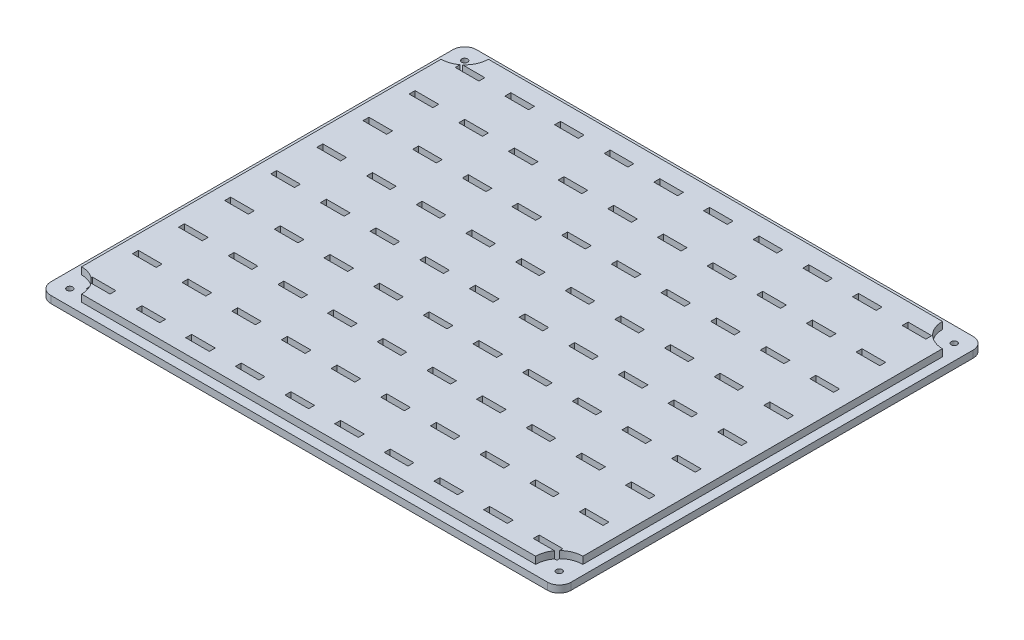
SolidWorks part; units mm, degrees
ref_plane "Front Plane" through (0, 0, 0) normal (0, 0, 1) x (1, 0, 0)
ref_plane "Top Plane" through (0, 0, 0) normal (0, 1, 0) x (1, 0, 0)
ref_plane "Right Plane" through (0, 0, 0) normal (1, 0, 0) x (0, 0, -1)
sketch "Sketch1" plane through (0, 0, 0) normal (0, 1, 0) x (1, 0, 0)
  line L1 (0, 0) -> (220, 0)
  line L2 (0, 0) -> (0, 180)
  line L3 (0, 180) -> (220, 180)
  line L4 (220, 0) -> (220, 180)
  dimension "D1" = 220
  dimension "D2" = 180
extrude "Boss-Extrude1" add sketch "Sketch1" along normal blind 3
fillet "Fillet1" radius 5 4 edges at (0, 1.5, -180) (0, 1.5, 0) (220, 1.5, -180) (220, 1.5, 0)
sketch "Sketch7" plane through (0, 3, 0) normal (0, 1, 0) x (1, 0, 0)
  line L0 (110, 187.4123) -> (110, -2.139) construction
  line L1 (-6.8646, 90) -> (231.1986, 90) construction
  line L2 (206, 176) -> (14, 176)
  line L3 (216, 166) -> (216, 14)
  line L4 (215, 180) -> (5, 180) construction
  line L5 (220, 5) -> (220, 175) construction
  line L6 (206, 4) -> (14, 4)
  line L7 (4, 166) -> (4, 14)
  line L8 (0, 175) -> (0, 5) construction
  line L9 (5, 0) -> (215, 0) construction
  arc A0 (206, 176) -> (216, 166) centre (216, 176) ccw
  arc A1 (206, 4) -> (216, 14) centre (216, 4) cw
  arc A2 (14, 4) -> (4, 14) centre (4, 4) ccw
  arc A3 (14, 176) -> (4, 166) centre (4, 176) cw
  point P14 (216, 90)
  point P18 (110, 4)
  point P23 (110, 176)
  dimension "D5" = 4
  dimension "D1" = 4
  dimension "D2" = 4
  dimension "D3" = 14
  dimension "D4" = 14
  dimension "D6" = 4
extrude "Boss-Extrude2" add sketch "Sketch7" along normal blind 3
sketch "Sketch8" plane through (0, 3, 0) normal (0, 1, 0) x (1, 0, 0)
  line L0 (110, 176) -> (110, 4) construction
  line L1 (206, 176) -> (14, 176) construction
  line L2 (14, 4) -> (206, 4) construction
  line L3 (4, 90) -> (216, 90) construction
  line L4 (4, 166) -> (4, 14) construction
  line L5 (216, 14) -> (216, 166) construction
  line L6 (215, 180) -> (5, 180) construction
  line L7 (0, 175) -> (0, 5) construction
  circle A0 centre (6.5, 173.5) radius 1.25
  circle A1 centre (213.5, 173.5) radius 1.25
  circle A2 centre (213.5, 6.5) radius 1.25
  circle A3 centre (6.5, 6.5) radius 1.25
  dimension "D2" = 6.5
  dimension "D3" = 6.5
extrude "Cut-Extrude3" cut sketch "Sketch8" against normal through all
sketch "Sketch9" plane through (0, 0, 0) normal (0, -1, 0) x (1, 0, 0)
  line L6 (31, -10) -> (31, -12.5)
  line L9 (31, -10) -> (41, -10)
  line L10 (10, -10) -> (20, -10)
  line L11 (10, -10) -> (10, -12.5)
  line L12 (10, -12.5) -> (20, -12.5)
  line L13 (20, -10) -> (20, -12.5)
  line L14 (41, -10) -> (41, -12.5)
  line L15 (31, -12.5) -> (41, -12.5)
  line L16 (52, -10) -> (52, -12.5)
  line L17 (52, -10) -> (62, -10)
  line L18 (62, -10) -> (62, -12.5)
  line L19 (52, -12.5) -> (62, -12.5)
  line L20 (73, -10) -> (73, -12.5)
  line L21 (73, -10) -> (83, -10)
  line L22 (83, -10) -> (83, -12.5)
  line L23 (73, -12.5) -> (83, -12.5)
  line L24 (94, -10) -> (94, -12.5)
  line L25 (94, -10) -> (104, -10)
  line L26 (104, -10) -> (104, -12.5)
  line L27 (94, -12.5) -> (104, -12.5)
  line L28 (115, -10) -> (115, -12.5)
  line L29 (115, -10) -> (125, -10)
  line L30 (125, -10) -> (125, -12.5)
  line L31 (115, -12.5) -> (125, -12.5)
  line L32 (136, -10) -> (136, -12.5)
  line L33 (136, -10) -> (146, -10)
  line L34 (146, -10) -> (146, -12.5)
  line L35 (136, -12.5) -> (146, -12.5)
  line L36 (157, -10) -> (157, -12.5)
  line L37 (157, -10) -> (167, -10)
  line L38 (167, -10) -> (167, -12.5)
  line L39 (157, -12.5) -> (167, -12.5)
  line L40 (178, -10) -> (178, -12.5)
  line L41 (178, -10) -> (188, -10)
  line L42 (188, -10) -> (188, -12.5)
  line L43 (178, -12.5) -> (188, -12.5)
  line L44 (199, -10) -> (199, -12.5)
  line L45 (199, -10) -> (209, -10)
  line L46 (209, -10) -> (209, -12.5)
  line L47 (199, -12.5) -> (209, -12.5)
  line L48 (31, -29.5) -> (31, -32)
  line L49 (31, -29.5) -> (41, -29.5)
  line L50 (41, -29.5) -> (41, -32)
  line L51 (31, -32) -> (41, -32)
  line L52 (52, -29.5) -> (52, -32)
  line L53 (52, -29.5) -> (62, -29.5)
  line L54 (62, -29.5) -> (62, -32)
  line L55 (52, -32) -> (62, -32)
  line L56 (73, -29.5) -> (73, -32)
  line L57 (73, -29.5) -> (83, -29.5)
  line L58 (83, -29.5) -> (83, -32)
  line L59 (73, -32) -> (83, -32)
  line L60 (94, -29.5) -> (94, -32)
  line L61 (94, -29.5) -> (104, -29.5)
  line L62 (104, -29.5) -> (104, -32)
  line L63 (94, -32) -> (104, -32)
  line L64 (115, -29.5) -> (115, -32)
  line L65 (115, -29.5) -> (125, -29.5)
  line L66 (125, -29.5) -> (125, -32)
  line L67 (115, -32) -> (125, -32)
  line L68 (136, -29.5) -> (136, -32)
  line L69 (136, -29.5) -> (146, -29.5)
  line L70 (146, -29.5) -> (146, -32)
  line L71 (136, -32) -> (146, -32)
  line L72 (157, -29.5) -> (157, -32)
  line L73 (157, -29.5) -> (167, -29.5)
  line L74 (167, -29.5) -> (167, -32)
  line L75 (157, -32) -> (167, -32)
  line L76 (178, -29.5) -> (178, -32)
  line L77 (178, -29.5) -> (188, -29.5)
  line L78 (188, -29.5) -> (188, -32)
  line L79 (178, -32) -> (188, -32)
  line L80 (199, -29.5) -> (199, -32)
  line L81 (199, -29.5) -> (209, -29.5)
  line L82 (209, -29.5) -> (209, -32)
  line L83 (199, -32) -> (209, -32)
  line L84 (31, -49) -> (31, -51.5)
  line L85 (31, -49) -> (41, -49)
  line L86 (41, -49) -> (41, -51.5)
  line L87 (31, -51.5) -> (41, -51.5)
  line L88 (52, -49) -> (52, -51.5)
  line L89 (52, -49) -> (62, -49)
  line L90 (62, -49) -> (62, -51.5)
  line L91 (52, -51.5) -> (62, -51.5)
  line L92 (73, -49) -> (73, -51.5)
  line L93 (73, -49) -> (83, -49)
  line L94 (83, -49) -> (83, -51.5)
  line L95 (73, -51.5) -> (83, -51.5)
  line L96 (94, -49) -> (94, -51.5)
  line L97 (94, -49) -> (104, -49)
  line L98 (104, -49) -> (104, -51.5)
  line L99 (94, -51.5) -> (104, -51.5)
  line L100 (115, -49) -> (115, -51.5)
  line L101 (115, -49) -> (125, -49)
  line L102 (125, -49) -> (125, -51.5)
  line L103 (115, -51.5) -> (125, -51.5)
  line L104 (136, -49) -> (136, -51.5)
  line L105 (136, -49) -> (146, -49)
  line L106 (146, -49) -> (146, -51.5)
  line L107 (136, -51.5) -> (146, -51.5)
  line L108 (157, -49) -> (157, -51.5)
  line L109 (157, -49) -> (167, -49)
  line L110 (167, -49) -> (167, -51.5)
  line L111 (157, -51.5) -> (167, -51.5)
  line L112 (178, -49) -> (178, -51.5)
  line L113 (178, -49) -> (188, -49)
  line L114 (188, -49) -> (188, -51.5)
  line L115 (178, -51.5) -> (188, -51.5)
  line L116 (199, -49) -> (199, -51.5)
  line L117 (199, -49) -> (209, -49)
  line L118 (209, -49) -> (209, -51.5)
  line L119 (199, -51.5) -> (209, -51.5)
  line L120 (31, -68.5) -> (31, -71)
  line L121 (31, -68.5) -> (41, -68.5)
  line L122 (41, -68.5) -> (41, -71)
  line L123 (31, -71) -> (41, -71)
  line L124 (52, -68.5) -> (52, -71)
  line L125 (52, -68.5) -> (62, -68.5)
  line L126 (62, -68.5) -> (62, -71)
  line L127 (52, -71) -> (62, -71)
  line L128 (73, -68.5) -> (73, -71)
  line L129 (73, -68.5) -> (83, -68.5)
  line L130 (83, -68.5) -> (83, -71)
  line L131 (73, -71) -> (83, -71)
  line L132 (94, -68.5) -> (94, -71)
  line L133 (94, -68.5) -> (104, -68.5)
  line L134 (104, -68.5) -> (104, -71)
  line L135 (94, -71) -> (104, -71)
  line L136 (115, -68.5) -> (115, -71)
  line L137 (115, -68.5) -> (125, -68.5)
  line L138 (125, -68.5) -> (125, -71)
  line L139 (115, -71) -> (125, -71)
  line L140 (136, -68.5) -> (136, -71)
  line L141 (136, -68.5) -> (146, -68.5)
  line L142 (146, -68.5) -> (146, -71)
  line L143 (136, -71) -> (146, -71)
  line L144 (157, -68.5) -> (157, -71)
  line L145 (157, -68.5) -> (167, -68.5)
  line L146 (167, -68.5) -> (167, -71)
  line L147 (157, -71) -> (167, -71)
  line L148 (178, -68.5) -> (178, -71)
  line L149 (178, -68.5) -> (188, -68.5)
  line L150 (188, -68.5) -> (188, -71)
  line L151 (178, -71) -> (188, -71)
  line L152 (199, -68.5) -> (199, -71)
  line L153 (199, -68.5) -> (209, -68.5)
  line L154 (209, -68.5) -> (209, -71)
  line L155 (199, -71) -> (209, -71)
  line L156 (31, -88) -> (31, -90.5)
  line L157 (31, -88) -> (41, -88)
  line L158 (41, -88) -> (41, -90.5)
  line L159 (31, -90.5) -> (41, -90.5)
  line L160 (52, -88) -> (52, -90.5)
  line L161 (52, -88) -> (62, -88)
  line L162 (62, -88) -> (62, -90.5)
  line L163 (52, -90.5) -> (62, -90.5)
  line L164 (73, -88) -> (73, -90.5)
  line L165 (73, -88) -> (83, -88)
  line L166 (83, -88) -> (83, -90.5)
  line L167 (73, -90.5) -> (83, -90.5)
  line L168 (94, -88) -> (94, -90.5)
  line L169 (94, -88) -> (104, -88)
  line L170 (104, -88) -> (104, -90.5)
  line L171 (94, -90.5) -> (104, -90.5)
  line L172 (115, -88) -> (115, -90.5)
  line L173 (115, -88) -> (125, -88)
  line L174 (125, -88) -> (125, -90.5)
  line L175 (115, -90.5) -> (125, -90.5)
  line L176 (136, -88) -> (136, -90.5)
  line L177 (136, -88) -> (146, -88)
  line L178 (146, -88) -> (146, -90.5)
  line L179 (136, -90.5) -> (146, -90.5)
  line L180 (157, -88) -> (157, -90.5)
  line L181 (157, -88) -> (167, -88)
  line L182 (167, -88) -> (167, -90.5)
  line L183 (157, -90.5) -> (167, -90.5)
  line L184 (178, -88) -> (178, -90.5)
  line L185 (178, -88) -> (188, -88)
  line L186 (188, -88) -> (188, -90.5)
  line L187 (178, -90.5) -> (188, -90.5)
  line L188 (199, -88) -> (199, -90.5)
  line L189 (199, -88) -> (209, -88)
  line L190 (209, -88) -> (209, -90.5)
  line L191 (199, -90.5) -> (209, -90.5)
  line L192 (31, -107.5) -> (31, -110)
  line L193 (31, -107.5) -> (41, -107.5)
  line L194 (41, -107.5) -> (41, -110)
  line L195 (31, -110) -> (41, -110)
  line L196 (52, -107.5) -> (52, -110)
  line L197 (52, -107.5) -> (62, -107.5)
  line L198 (62, -107.5) -> (62, -110)
  line L199 (52, -110) -> (62, -110)
  line L200 (73, -107.5) -> (73, -110)
  line L201 (73, -107.5) -> (83, -107.5)
  line L202 (83, -107.5) -> (83, -110)
  line L203 (73, -110) -> (83, -110)
  line L204 (94, -107.5) -> (94, -110)
  line L205 (94, -107.5) -> (104, -107.5)
  line L206 (104, -107.5) -> (104, -110)
  line L207 (94, -110) -> (104, -110)
  line L208 (115, -107.5) -> (115, -110)
  line L209 (115, -107.5) -> (125, -107.5)
  line L210 (125, -107.5) -> (125, -110)
  line L211 (115, -110) -> (125, -110)
  line L212 (136, -107.5) -> (136, -110)
  line L213 (136, -107.5) -> (146, -107.5)
  line L214 (146, -107.5) -> (146, -110)
  line L215 (136, -110) -> (146, -110)
  line L216 (157, -107.5) -> (157, -110)
  line L217 (157, -107.5) -> (167, -107.5)
  line L218 (167, -107.5) -> (167, -110)
  line L219 (157, -110) -> (167, -110)
  line L220 (178, -107.5) -> (178, -110)
  line L221 (178, -107.5) -> (188, -107.5)
  line L222 (188, -107.5) -> (188, -110)
  line L223 (178, -110) -> (188, -110)
  line L224 (199, -107.5) -> (199, -110)
  line L225 (199, -107.5) -> (209, -107.5)
  line L226 (209, -107.5) -> (209, -110)
  line L227 (199, -110) -> (209, -110)
  line L228 (31, -127) -> (31, -129.5)
  line L229 (31, -127) -> (41, -127)
  line L230 (41, -127) -> (41, -129.5)
  line L231 (31, -129.5) -> (41, -129.5)
  line L232 (52, -127) -> (52, -129.5)
  line L233 (52, -127) -> (62, -127)
  line L234 (62, -127) -> (62, -129.5)
  line L235 (52, -129.5) -> (62, -129.5)
  line L236 (73, -127) -> (73, -129.5)
  line L237 (73, -127) -> (83, -127)
  line L238 (83, -127) -> (83, -129.5)
  line L239 (73, -129.5) -> (83, -129.5)
  line L240 (94, -127) -> (94, -129.5)
  line L241 (94, -127) -> (104, -127)
  line L242 (104, -127) -> (104, -129.5)
  line L243 (94, -129.5) -> (104, -129.5)
  line L244 (115, -127) -> (115, -129.5)
  line L245 (115, -127) -> (125, -127)
  line L246 (125, -127) -> (125, -129.5)
  line L247 (115, -129.5) -> (125, -129.5)
  line L248 (136, -127) -> (136, -129.5)
  line L249 (136, -127) -> (146, -127)
  line L250 (146, -127) -> (146, -129.5)
  line L251 (136, -129.5) -> (146, -129.5)
  line L252 (157, -127) -> (157, -129.5)
  line L253 (157, -127) -> (167, -127)
  line L254 (167, -127) -> (167, -129.5)
  line L255 (157, -129.5) -> (167, -129.5)
  line L256 (178, -127) -> (178, -129.5)
  line L257 (178, -127) -> (188, -127)
  line L258 (188, -127) -> (188, -129.5)
  line L259 (178, -129.5) -> (188, -129.5)
  line L260 (199, -127) -> (199, -129.5)
  line L261 (199, -127) -> (209, -127)
  line L262 (209, -127) -> (209, -129.5)
  line L263 (199, -129.5) -> (209, -129.5)
  line L264 (31, -146.5) -> (31, -149)
  line L265 (31, -146.5) -> (41, -146.5)
  line L266 (41, -146.5) -> (41, -149)
  line L267 (31, -149) -> (41, -149)
  line L268 (52, -146.5) -> (52, -149)
  line L269 (52, -146.5) -> (62, -146.5)
  line L270 (62, -146.5) -> (62, -149)
  line L271 (52, -149) -> (62, -149)
  line L272 (73, -146.5) -> (73, -149)
  line L273 (73, -146.5) -> (83, -146.5)
  line L274 (83, -146.5) -> (83, -149)
  line L275 (73, -149) -> (83, -149)
  line L276 (94, -146.5) -> (94, -149)
  line L277 (94, -146.5) -> (104, -146.5)
  line L278 (104, -146.5) -> (104, -149)
  line L279 (94, -149) -> (104, -149)
  line L280 (115, -146.5) -> (115, -149)
  line L281 (115, -146.5) -> (125, -146.5)
  line L282 (125, -146.5) -> (125, -149)
  line L283 (115, -149) -> (125, -149)
  line L284 (136, -146.5) -> (136, -149)
  line L285 (136, -146.5) -> (146, -146.5)
  line L286 (146, -146.5) -> (146, -149)
  line L287 (136, -149) -> (146, -149)
  line L288 (157, -146.5) -> (157, -149)
  line L289 (157, -146.5) -> (167, -146.5)
  line L290 (167, -146.5) -> (167, -149)
  line L291 (157, -149) -> (167, -149)
  line L292 (178, -146.5) -> (178, -149)
  line L293 (178, -146.5) -> (188, -146.5)
  line L294 (188, -146.5) -> (188, -149)
  line L295 (178, -149) -> (188, -149)
  line L296 (199, -146.5) -> (199, -149)
  line L297 (199, -146.5) -> (209, -146.5)
  line L298 (209, -146.5) -> (209, -149)
  line L299 (199, -149) -> (209, -149)
  line L300 (31, -166) -> (31, -168.5)
  line L301 (31, -166) -> (41, -166)
  line L302 (41, -166) -> (41, -168.5)
  line L303 (31, -168.5) -> (41, -168.5)
  line L304 (52, -166) -> (52, -168.5)
  line L305 (52, -166) -> (62, -166)
  line L306 (62, -166) -> (62, -168.5)
  line L307 (52, -168.5) -> (62, -168.5)
  line L308 (73, -166) -> (73, -168.5)
  line L309 (73, -166) -> (83, -166)
  line L310 (83, -166) -> (83, -168.5)
  line L311 (73, -168.5) -> (83, -168.5)
  line L312 (94, -166) -> (94, -168.5)
  line L313 (94, -166) -> (104, -166)
  line L314 (104, -166) -> (104, -168.5)
  line L315 (94, -168.5) -> (104, -168.5)
  line L316 (115, -166) -> (115, -168.5)
  line L317 (115, -166) -> (125, -166)
  line L318 (125, -166) -> (125, -168.5)
  line L319 (115, -168.5) -> (125, -168.5)
  line L320 (136, -166) -> (136, -168.5)
  line L321 (136, -166) -> (146, -166)
  line L322 (146, -166) -> (146, -168.5)
  line L323 (136, -168.5) -> (146, -168.5)
  line L324 (157, -166) -> (157, -168.5)
  line L325 (157, -166) -> (167, -166)
  line L326 (167, -166) -> (167, -168.5)
  line L327 (157, -168.5) -> (167, -168.5)
  line L328 (178, -166) -> (178, -168.5)
  line L329 (178, -166) -> (188, -166)
  line L330 (188, -166) -> (188, -168.5)
  line L331 (178, -168.5) -> (188, -168.5)
  line L332 (199, -166) -> (199, -168.5)
  line L333 (199, -166) -> (209, -166)
  line L334 (209, -166) -> (209, -168.5)
  line L335 (199, -168.5) -> (209, -168.5)
  line L336 (10, -29.5) -> (10, -32)
  line L337 (10, -29.5) -> (20, -29.5)
  line L338 (20, -29.5) -> (20, -32)
  line L339 (10, -32) -> (20, -32)
  line L340 (10, -49) -> (10, -51.5)
  line L341 (10, -49) -> (20, -49)
  line L342 (20, -49) -> (20, -51.5)
  line L343 (10, -51.5) -> (20, -51.5)
  line L344 (10, -68.5) -> (10, -71)
  line L345 (10, -68.5) -> (20, -68.5)
  line L346 (20, -68.5) -> (20, -71)
  line L347 (10, -71) -> (20, -71)
  line L348 (10, -88) -> (10, -90.5)
  line L349 (10, -88) -> (20, -88)
  line L350 (20, -88) -> (20, -90.5)
  line L351 (10, -90.5) -> (20, -90.5)
  line L352 (10, -107.5) -> (10, -110)
  line L353 (10, -107.5) -> (20, -107.5)
  line L354 (20, -107.5) -> (20, -110)
  line L355 (10, -110) -> (20, -110)
  line L356 (10, -127) -> (10, -129.5)
  line L357 (10, -127) -> (20, -127)
  line L358 (20, -127) -> (20, -129.5)
  line L359 (10, -129.5) -> (20, -129.5)
  line L360 (10, -146.5) -> (10, -149)
  line L361 (10, -146.5) -> (20, -146.5)
  line L362 (20, -146.5) -> (20, -149)
  line L363 (10, -149) -> (20, -149)
  line L364 (10, -166) -> (10, -168.5)
  line L365 (10, -166) -> (20, -166)
  line L366 (20, -166) -> (20, -168.5)
  line L367 (10, -168.5) -> (20, -168.5)
  point P16 (0, 0)
  dimension "D5" = 10
  dimension "D6" = 2.5
  dimension "D8" = 10
  dimension "D9" = 10
  dimension "D10" = 9
extrude "Cut-Extrude4" cut sketch "Sketch9" against normal through all
